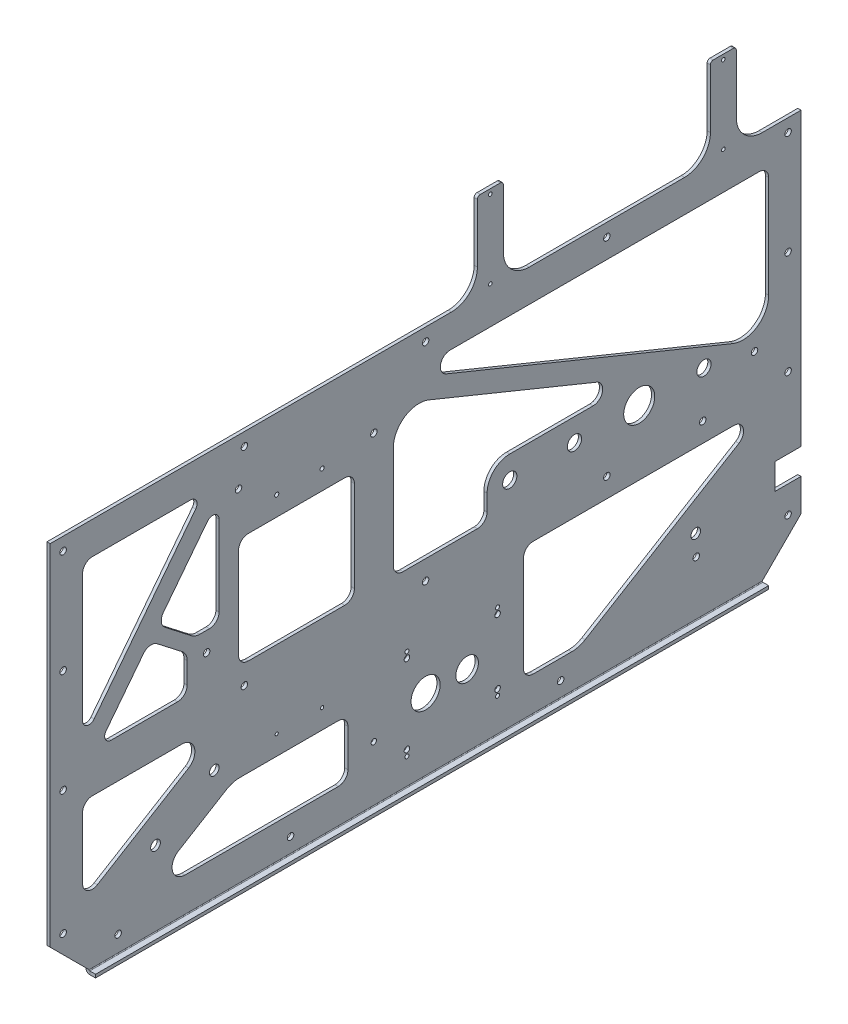
SolidWorks part; units mm, degrees
note: The reader was unsure of these and kept them because the rebuilt part matched: flange length of "Edge-Flange1".
material "6061-T6 (SS)"
ref_plane "Front Plane" through (0, 0, 0) normal (0, 0, 1) x (1, 0, 0)
ref_plane "Top Plane" through (0, 0, 0) normal (0, 1, 0) x (1, 0, 0)
ref_plane "Right Plane" through (0, 0, 0) normal (1, 0, 0) x (0, 0, -1)
sketch "Sketch1" plane through (0, 0, 0) normal (1, 0, 0) x (0, 0, -1)
  line L0 (330.2, 0) -> (-330.2, 0)
  line L1 (-330.2, 0) -> (-368.3, 38.1)
  line L2 (-368.3, 38.1) -> (-368.3, 381)
  line L3 (-368.3, 381) -> (368.3, 381)
  line L4 (368.3, 381) -> (368.3, 38.1)
  line L5 (368.3, 38.1) -> (330.2, 0)
  point P4 (0, 0)
  dimension "D1" = 736.6
  dimension "D2" = 381
  dimension "D3" = 38.1
  dimension "D4" = 45
base flange "Base-Flange1" sketch "Sketch1" thickness 3.175 reverse thickness direction no parameters "D1"=0.7366
sketch "Sketch10" plane through (0, 0, 0) normal (1, 0, 0) x (0, 0, -1)
  line L0 (302.006, 466.725) -> (282.194, 466.725) construction
  line L1 (304.8, 381) -> (279.4, 381)
  line L2 (304.8, 381) -> (304.8, 466.725)
  line L3 (304.8, 466.725) -> (279.4, 466.725)
  line L4 (279.4, 381) -> (279.4, 466.725)
  line L5 (279.4, 463.931) -> (279.4, 406.4) construction
  line L7 (368.3, 381) -> (-368.3, 381) construction
  line L8 (304.8, 406.4) -> (304.8, 463.931) construction
  line L9 (76.2, 381) -> (50.8, 381)
  line L10 (76.2, 381) -> (76.2, 466.725)
  line L11 (76.2, 466.725) -> (50.8, 466.725)
  line L12 (50.8, 381) -> (50.8, 466.725)
  line L13 (76.2, 406.4) -> (76.2, 463.931) construction
  line L15 (50.8, 463.931) -> (50.8, 406.4) construction
base flange "Tab1" sketch "Sketch10" thickness 3.175 reverse thickness direction no parameters "D1"=0.7366
sketch "Sketch6" plane through (0, 0, 0) normal (1, 0, 0) x (0, 0, -1)
  circle A0 centre (264.9792, 73.025) radius 4.7625
  circle A1 centre (0, 69.85) radius 14.2875
  circle A2 centre (-264.9792, 73.025) radius 4.7625
  circle A3 centre (132.4896, 14.2875) radius 3.175 construction
  circle A4 centre (-132.4896, 14.2875) radius 3.175 construction
  circle A5 centre (132.4896, 14.2875) radius 3.175
  circle A6 centre (-264.9792, 73.025) radius 4.7625 construction
  circle A7 centre (0, 69.85) radius 14.2875 construction
  circle A8 centre (264.9792, 73.025) radius 4.7625 construction
  circle A9 centre (-132.4896, 14.2875) radius 3.175
  dimension "D1" = 28.575
  dimension "D2" = 9.525
  dimension "D3" = 9.525
extrude "Cut-Extrude1" cut sketch "Sketch6" against normal through all normal cut yes
sketch "Sketch7" plane through (0, 0, 0) normal (1, 0, 0) x (0, 0, -1)
  line L0 (368.3, 95.25) -> (368.3, 69.85)
  line L1 (209.55, 209.55) -> (146.05, 209.55) construction
  line L2 (368.3, 95.25) -> (342.9, 95.25)
  line L3 (146.05, 209.55) -> (82.55, 209.55) construction
  line L4 (368.3, 69.85) -> (342.9, 69.85)
  line L7 (342.9, 95.25) -> (342.9, 69.85)
  line L8 (349.2669, 95.25) -> (346.0496, 95.25) construction
  line L10 (342.9, 92.1004) -> (342.9, 88.8831) construction
  circle A0 centre (355.6, 43.3605) radius 3.175 construction
  circle A1 centre (355.6, 165.1) radius 3.175 construction
  circle A2 centre (177.8, 165.1) radius 3.175 construction
  circle A3 centre (0, 165.1) radius 3.175 construction
  circle A4 centre (-177.8, 165.1) radius 3.175 construction
  circle A5 centre (-355.6, 43.3605) radius 3.175 construction
  circle A6 centre (-355.6, 165.1) radius 3.175 construction
  circle A7 centre (355.6, 43.3605) radius 3.175
  circle A8 centre (355.6, 165.1) radius 3.175
  circle A9 centre (177.8, 165.1) radius 3.175
  circle A10 centre (0, 165.1) radius 3.175
  circle A11 centre (-177.8, 165.1) radius 3.175
  circle A12 centre (-355.6, 43.3605) radius 3.175
  circle A13 centre (-355.6, 165.1) radius 3.175
  circle A14 centre (-301.625, 15.875) radius 3.175 construction
  circle A15 centre (-214.8334, 211.6192) radius 3.175 construction
  circle A16 centre (-301.625, 15.875) radius 3.175
  circle A17 centre (-214.8334, 211.6192) radius 3.175
  circle A18 centre (-101.6, 311.4675) radius 2.032 construction
  circle A19 centre (-146.05, 311.4675) radius 2.032 construction
  circle A20 centre (-101.6, 311.4675) radius 2.032
  circle A21 centre (-146.05, 311.4675) radius 2.032
  circle A22 centre (82.55, 209.55) radius 6.985
  circle A23 centre (63.5, 461.9625) radius 1.7859 construction
  circle A24 centre (265.525, 52.775) radius 3.175 construction
  circle A25 centre (63.5, 385.7625) radius 1.7859 construction
  circle A26 centre (-146.05, 108.2675) radius 1.5875 construction
  circle A27 centre (-101.6, 108.2675) radius 1.5875 construction
  circle A28 centre (-146.05, 108.2675) radius 1.5875
  circle A29 centre (-101.6, 108.2675) radius 1.5875
  circle A30 centre (273.05, 209.55) radius 6.985
  circle A31 centre (209.55, 209.55) radius 15.24
  circle A32 centre (146.05, 209.55) radius 6.985
  circle A33 centre (271.875, 165.1) radius 3.175 construction
  circle A34 centre (273.05, 209.55) radius 6.9024 construction
  circle A35 centre (146.05, 209.55) radius 6.9024 construction
  circle A36 centre (209.55, 209.55) radius 13.97 construction
  circle A37 centre (292.1, 461.9625) radius 1.7859 construction
  circle A38 centre (355.6, 266.7) radius 3.175 construction
  circle A39 centre (322.675, 198.825) radius 3.175 construction
  circle A40 centre (265.525, 52.775) radius 3.175
  circle A41 centre (271.875, 165.1) radius 3.175
  circle A42 centre (292.1, 385.7625) radius 1.7859 construction
  circle A43 centre (63.5, 461.9625) radius 1.7859
  circle A44 centre (-50.8, 316.23) radius 3.175 construction
  circle A45 centre (-50.8, 316.23) radius 3.175
  circle A46 centre (355.6, 368.3) radius 3.175 construction
  circle A47 centre (177.8, 368.3) radius 3.175 construction
  circle A48 centre (0, 368.3) radius 3.175 construction
  circle A49 centre (-177.8, 368.3) radius 3.175 construction
  circle A50 centre (-355.6, 368.3) radius 3.175 construction
  circle A51 centre (-355.6, 266.7) radius 3.175 construction
  circle A52 centre (355.6, 266.7) radius 3.175
  circle A53 centre (355.6, 368.3) radius 3.175
  circle A54 centre (177.8, 368.3) radius 3.175
  circle A55 centre (0, 368.3) radius 3.175
  circle A56 centre (-177.8, 368.3) radius 3.175
  circle A57 centre (-355.6, 368.3) radius 3.175
  circle A58 centre (-355.6, 266.7) radius 3.175
  circle A59 centre (322.675, 198.825) radius 3.175
  circle A62 centre (292.1, 461.9625) radius 1.7859
  circle A63 centre (63.5, 385.7625) radius 1.7859
  circle A64 centre (292.1, 385.7625) radius 1.7859
  dimension "D4" = 13.97
  dimension "D5" = 30.48
  dimension "D1" = 25.4
extrude "Cut-Extrude2" cut sketch "Sketch7" against normal through all normal cut yes
sketch "Sketch8" plane through (0, 0, 0) normal (1, 0, 0) x (0, 0, -1)
  circle A0 centre (70.5879, 107.442) radius 1.9514 construction
  circle A1 centre (70.5879, 101.6) radius 2.7261 construction
  circle A2 centre (-18.3121, 114.427) radius 1.9514 construction
  circle A3 centre (-18.3121, 108.585) radius 2.7261 construction
  circle A4 centre (-18.3121, 31.115) radius 2.7261 construction
  circle A5 centre (-18.3121, 25.273) radius 1.9514 construction
  circle A6 centre (70.5879, 38.1) radius 2.7261 construction
  circle A7 centre (70.5879, 32.258) radius 1.9514 construction
  circle A8 centre (70.5879, 107.442) radius 1.9514
  circle A9 centre (70.5879, 101.6) radius 2.7261
  circle A10 centre (-18.3121, 114.427) radius 1.9514
  circle A11 centre (-18.3121, 108.585) radius 2.7261
  circle A12 centre (-18.3121, 31.115) radius 2.7261
  circle A13 centre (-18.3121, 25.273) radius 1.9514
  circle A14 centre (70.5879, 38.1) radius 2.7261
  circle A15 centre (70.5879, 32.258) radius 1.9514
  circle A16 centre (40.7162, 69.85) radius 11.1125 construction
  circle A17 centre (40.7162, 69.85) radius 11.1125
extrude "Cut-Extrude3" cut sketch "Sketch8" against normal through all normal cut yes
sketch "Sketch9" plane through (0, 0, 0) normal (1, 0, 0) x (0, 0, -1)
  circle A0 centre (-207.3469, 108.0375) radius 4.7625 construction
  circle A1 centre (-183.5344, 335.05) radius 3.175 construction
  circle A2 centre (-183.5344, 335.05) radius 3.175
  circle A3 centre (-207.3469, 108.0375) radius 4.7625
  circle A4 centre (-50.8, 53.975) radius 2.6035 construction
  circle A5 centre (-50.8, 53.975) radius 2.6035
extrude "Cut-Extrude4" cut sketch "Sketch9" against normal through all normal cut yes
fillet "Fillet1" [suppressed] radius 1.5875
fillet "Fillet2" radius 2.794 4 edges at (-1.5875, 466.725, -279.4) (-1.5875, 466.725, -304.8) (-1.5875, 466.725, -76.2) (-1.5875, 466.725, -50.8)
fillet "Fillet3" radius 25.4 4 edges at (-1.5875, 381, -279.4) (-1.5875, 381, -304.8) (-1.5875, 381, -76.2) (-1.5875, 381, -50.8)
sketch "Sketch11" plane through (0, 0, 0) normal (1, 0, 0) x (0, 0, -1)
  line L0 (-355.6, 165.1) -> (-355.6, 368.3) construction
  line L1 (-355.6, 368.3) -> (355.6, 368.3) construction
  line L2 (355.6, 368.3) -> (355.6, 165.1) construction
  line L3 (327.025, 349.25) -> (23.9702, 349.25) construction
  line L4 (20.3691, 330.907) -> (301.5471, 216.0804) construction
  line L5 (336.55, 239.5952) -> (336.55, 339.725) construction
  line L6 (327.025, 349.25) -> (23.9702, 349.25)
  line L7 (20.3691, 330.907) -> (301.5471, 216.0804)
  line L8 (336.55, 239.5952) -> (336.55, 339.725)
  line L10 (302.4269, 146.05) -> (105.5129, 146.05) construction
  line L12 (-355.6, 165.1) -> (355.6, 165.1) construction
  line L13 (95.9879, 136.525) -> (95.9879, 42.8625) construction
  line L14 (156.451, 37.0096) -> (307.36, 128.377) construction
  line L15 (105.5129, 33.3375) -> (143.2959, 33.3375) construction
  line L16 (302.4269, 146.05) -> (105.5129, 146.05)
  line L17 (95.9879, 136.525) -> (95.9879, 42.8625)
  line L18 (156.451, 37.0096) -> (307.36, 128.377)
  line L19 (105.5129, 33.3375) -> (143.2959, 33.3375)
  line L20 (-236.0213, 33.3375) -> (-85.725, 33.3375) construction
  line L21 (-76.2, 42.8625) -> (-76.2, 79.6925) construction
  line L22 (-85.725, 89.2175) -> (-182.2944, 89.2175) construction
  line L23 (-195.4823, 85.5255) -> (-242.6153, 56.8915) construction
  line L24 (-236.0213, 33.3375) -> (-85.725, 33.3375)
  line L25 (-76.2, 42.8625) -> (-76.2, 79.6925)
  line L26 (-85.725, 89.2175) -> (-182.2944, 89.2175)
  line L27 (-195.4823, 85.5255) -> (-242.6153, 56.8915)
  line L28 (-322.0795, 68.0556) -> (-232.4679, 122.496) construction
  line L29 (-239.0619, 146.05) -> (-327.025, 146.05) construction
  line L30 (-336.55, 136.525) -> (-336.55, 76.1961) construction
  line L31 (-322.0795, 68.0556) -> (-232.4679, 122.496)
  line L32 (-239.0619, 146.05) -> (-327.025, 146.05)
  line L33 (-336.55, 136.525) -> (-336.55, 76.1961)
  line L34 (-325.1809, 210.4894) -> (-225.5776, 339.0102) construction
  line L35 (-336.55, 339.725) -> (-336.55, 214.3792) construction
  line L36 (-230.5968, 349.25) -> (-327.025, 349.25) construction
  line L37 (-325.1809, 210.4894) -> (-225.5776, 339.0102)
  line L38 (-336.55, 339.725) -> (-336.55, 214.3792)
  line L39 (-230.5968, 349.25) -> (-327.025, 349.25)
  line L40 (-255.646, 253.5644) -> (-229.5382, 233.3309) construction
  line L41 (-221.7586, 230.6692) -> (-212.1094, 230.6692) construction
  line L42 (-202.5844, 240.1942) -> (-202.5844, 319.0208) construction
  line L43 (-213.9535, 322.9106) -> (-257.34, 266.9278) construction
  line L44 (-255.646, 253.5644) -> (-229.5382, 233.3309)
  line L45 (-221.7586, 230.6692) -> (-212.1094, 230.6692)
  line L46 (-202.5844, 240.1942) -> (-202.5844, 319.0208)
  line L47 (-213.9535, 322.9106) -> (-257.34, 266.9278)
  line L48 (-308.5376, 184.15) -> (-243.4084, 184.15) construction
  line L49 (-233.8834, 193.675) -> (-233.8834, 214.4059) construction
  line L50 (-238.8038, 224.4442) -> (-263.4257, 243.5261) construction
  line L51 (-276.7891, 241.8321) -> (-313.5567, 194.3898) construction
  line L52 (-308.5376, 184.15) -> (-243.4084, 184.15)
  line L53 (-233.8834, 193.675) -> (-233.8834, 214.4059)
  line L54 (-238.8038, 224.4442) -> (-263.4257, 243.5261)
  line L55 (-276.7891, 241.8321) -> (-313.5567, 194.3898)
  line L56 (-183.5344, 282.8925) -> (-183.5344, 193.675) construction
  line L57 (-174.0094, 184.15) -> (-79.375, 184.15) construction
  line L58 (-69.85, 193.675) -> (-69.85, 282.8925) construction
  line L59 (-79.375, 292.4175) -> (-174.0094, 292.4175) construction
  line L60 (-183.5344, 282.8925) -> (-183.5344, 193.675)
  line L61 (-174.0094, 184.15) -> (-79.375, 184.15)
  line L62 (-69.85, 193.675) -> (-69.85, 282.8925)
  line L63 (-79.375, 292.4175) -> (-174.0094, 292.4175)
  line L64 (-31.75, 293.8048) -> (-31.75, 193.675) construction
  line L65 (284.4309, 202.493) -> (3.2529, 317.3196) construction
  line L66 (-31.75, 293.8048) -> (-31.75, 193.675)
  line L67 (167.8106, 250.118) -> (3.2529, 317.3196)
  line L68 (164.2095, 231.775) -> (82.55, 231.775)
  line L69 (60.325, 209.55) -> (60.325, 193.675)
  line L70 (50.8, 184.15) -> (-22.225, 184.15)
  arc A0 (336.55, 339.725) -> (327.025, 349.25) centre (327.025, 339.725) ccw construction
  arc A1 (23.9702, 349.25) -> (20.3691, 330.907) centre (23.9702, 339.725) ccw construction
  arc A2 (301.5471, 216.0804) -> (336.55, 239.5952) centre (311.15, 239.5952) ccw construction
  arc A3 (336.55, 339.725) -> (327.025, 349.25) centre (327.025, 339.725) ccw
  arc A4 (23.9702, 349.25) -> (20.3691, 330.907) centre (23.9702, 339.725) ccw
  arc A5 (301.5471, 216.0804) -> (336.55, 239.5952) centre (311.15, 239.5952) ccw
  arc A6 (307.36, 128.377) -> (302.4269, 146.05) centre (302.4269, 136.525) ccw construction
  arc A7 (105.5129, 146.05) -> (95.9879, 136.525) centre (105.5129, 136.525) ccw construction
  arc A8 (143.2959, 33.3375) -> (156.451, 37.0096) centre (143.2959, 58.7375) ccw construction
  arc A9 (95.9879, 42.8625) -> (105.5129, 33.3375) centre (105.5129, 42.8625) ccw construction
  arc A10 (307.36, 128.377) -> (302.4269, 146.05) centre (302.4269, 136.525) ccw
  arc A12 (105.5129, 146.05) -> (95.9879, 136.525) centre (105.5129, 136.525) ccw
  arc A13 (143.2959, 33.3375) -> (156.451, 37.0096) centre (143.2959, 58.7375) ccw
  arc A16 (95.9879, 42.8625) -> (105.5129, 33.3375) centre (105.5129, 42.8625) ccw
  arc A17 (-242.6153, 56.8915) -> (-236.0213, 33.3375) centre (-236.0213, 46.0375) ccw construction
  arc A18 (-85.725, 33.3375) -> (-76.2, 42.8625) centre (-85.725, 42.8625) ccw construction
  arc A19 (-76.2, 79.6925) -> (-85.725, 89.2175) centre (-85.725, 79.6925) ccw construction
  arc A22 (-182.2944, 89.2175) -> (-195.4823, 85.5255) centre (-182.2944, 63.8175) ccw construction
  arc A23 (-242.6153, 56.8915) -> (-236.0213, 33.3375) centre (-236.0213, 46.0375) ccw
  arc A25 (-85.725, 33.3375) -> (-76.2, 42.8625) centre (-85.725, 42.8625) ccw
  arc A26 (-76.2, 79.6925) -> (-85.725, 89.2175) centre (-85.725, 79.6925) ccw
  arc A27 (-182.2944, 89.2175) -> (-195.4823, 85.5255) centre (-182.2944, 63.8175) ccw
  arc A28 (-336.55, 76.1961) -> (-322.0795, 68.0556) centre (-327.025, 76.1961) ccw construction
  arc A32 (-232.4679, 122.496) -> (-239.0619, 146.05) centre (-239.0619, 133.35) ccw construction
  arc A33 (-327.025, 146.05) -> (-336.55, 136.525) centre (-327.025, 136.525) ccw construction
  arc A34 (-336.55, 76.1961) -> (-322.0795, 68.0556) centre (-327.025, 76.1961) ccw
  arc A35 (-232.4679, 122.496) -> (-239.0619, 146.05) centre (-239.0619, 133.35) ccw
  arc A36 (-327.025, 146.05) -> (-336.55, 136.525) centre (-327.025, 136.525) ccw
  arc A37 (-336.55, 214.3792) -> (-325.1809, 210.4894) centre (-330.2, 214.3792) ccw construction
  arc A38 (-225.5776, 339.0102) -> (-230.5968, 349.25) centre (-230.5968, 342.9) ccw construction
  arc A39 (-327.025, 349.25) -> (-336.55, 339.725) centre (-327.025, 339.725) ccw construction
  arc A40 (-336.55, 214.3792) -> (-325.1809, 210.4894) centre (-330.2, 214.3792) ccw
  arc A41 (-225.5776, 339.0102) -> (-230.5968, 349.25) centre (-230.5968, 342.9) ccw
  arc A42 (-327.025, 349.25) -> (-336.55, 339.725) centre (-327.025, 339.725) ccw
  arc A43 (-257.34, 266.9278) -> (-255.646, 253.5644) centre (-249.8113, 261.0931) ccw construction
  arc A44 (-229.5382, 233.3309) -> (-221.7586, 230.6692) centre (-221.7586, 243.3692) ccw construction
  arc A45 (-212.1094, 230.6692) -> (-202.5844, 240.1942) centre (-212.1094, 240.1942) ccw construction
  arc A46 (-202.5844, 319.0208) -> (-213.9535, 322.9106) centre (-208.9344, 319.0208) ccw construction
  arc A47 (-257.34, 266.9278) -> (-255.646, 253.5644) centre (-249.8113, 261.0931) ccw
  arc A48 (-229.5382, 233.3309) -> (-221.7586, 230.6692) centre (-221.7586, 243.3692) ccw
  arc A49 (-212.1094, 230.6692) -> (-202.5844, 240.1942) centre (-212.1094, 240.1942) ccw
  arc A50 (-202.5844, 319.0208) -> (-213.9535, 322.9106) centre (-208.9344, 319.0208) ccw
  arc A51 (-243.4084, 184.15) -> (-233.8834, 193.675) centre (-243.4084, 193.675) ccw construction
  arc A52 (-233.8834, 214.4059) -> (-238.8038, 224.4442) centre (-246.5834, 214.4059) ccw construction
  arc A53 (-263.4257, 243.5261) -> (-276.7891, 241.8321) centre (-269.2604, 235.9974) ccw construction
  arc A54 (-313.5567, 194.3898) -> (-308.5376, 184.15) centre (-308.5376, 190.5) ccw construction
  arc A55 (-243.4084, 184.15) -> (-233.8834, 193.675) centre (-243.4084, 193.675) ccw
  arc A56 (-233.8834, 214.4059) -> (-238.8038, 224.4442) centre (-246.5834, 214.4059) ccw
  arc A57 (-263.4257, 243.5261) -> (-276.7891, 241.8321) centre (-269.2604, 235.9974) ccw
  arc A58 (-313.5567, 194.3898) -> (-308.5376, 184.15) centre (-308.5376, 190.5) ccw
  arc A59 (-174.0094, 292.4175) -> (-183.5344, 282.8925) centre (-174.0094, 282.8925) ccw construction
  arc A60 (-79.375, 184.15) -> (-69.85, 193.675) centre (-79.375, 193.675) ccw construction
  arc A61 (-183.5344, 193.675) -> (-174.0094, 184.15) centre (-174.0094, 193.675) ccw construction
  arc A62 (-69.85, 282.8925) -> (-79.375, 292.4175) centre (-79.375, 282.8925) ccw construction
  arc A63 (-174.0094, 292.4175) -> (-183.5344, 282.8925) centre (-174.0094, 282.8925) ccw
  arc A64 (-79.375, 184.15) -> (-69.85, 193.675) centre (-79.375, 193.675) ccw
  arc A65 (-183.5344, 193.675) -> (-174.0094, 184.15) centre (-174.0094, 193.675) ccw
  arc A66 (-69.85, 282.8925) -> (-79.375, 292.4175) centre (-79.375, 282.8925) ccw
  arc A67 (-31.75, 193.675) -> (-22.225, 184.15) centre (-22.225, 193.675) ccw construction
  arc A68 (3.2529, 317.3196) -> (-31.75, 293.8048) centre (-6.35, 293.8048) ccw construction
  arc A69 (-31.75, 193.675) -> (-22.225, 184.15) centre (-22.225, 193.675) ccw
  arc A70 (3.2529, 317.3196) -> (-31.75, 293.8048) centre (-6.35, 293.8048) ccw
  arc A71 (164.2095, 231.775) -> (167.8106, 250.118) centre (164.2095, 241.3) ccw
  arc A72 (82.55, 231.775) -> (60.325, 209.55) centre (82.55, 209.55) ccw
  arc A73 (60.325, 193.675) -> (50.8, 184.15) centre (50.8, 193.675) cw
  circle A74 centre (82.55, 209.55) radius 6.985 construction
  point P110 (209.55, 209.55)
  dimension "D1" = 22.225
extrude "Cut-Extrude5" cut sketch "Sketch11" against normal through all normal cut yes
sketch "Sketch12" plane through (-3.175, 0, 0) normal (-1, 0, 0) x (0, 0, 1)
  circle A0 centre (50.8, 316.23) radius 7.1633
  circle A1 centre (101.6, 311.4675) radius 5.9946
  circle A2 centre (146.05, 311.4675) radius 5.636
  circle A3 centre (101.6, 108.2675) radius 5.1307
  circle A4 centre (146.05, 108.2675) radius 4.8995
  circle A5 centre (50.8, 53.975) radius 6.7961
split line "Split Line1" [suppressed]
sketch "Sketch13" [suppressed] plane through (-3.175, 0, 0) normal (-1, 0, 0) x (0, 0, 1)
  line L0 (175.0557, 65.082) -> (99.2778, 65.082) construction
  line L1 (175.0557, 39.5069) -> (99.2778, 39.5069)
  line L2 (175.0557, 90.657) -> (99.2778, 90.657)
  line L3 (-286.6408, 115.1513) -> (-122.4649, 115.1513) construction
  line L4 (-286.6408, 140.992) -> (-122.4649, 140.992)
  line L5 (-286.6408, 89.3106) -> (-122.4649, 89.3106)
  line L6 (-286.6408, 39.5069) -> (-158.377, 39.5069) construction
  line L7 (-286.6408, 56.1499) -> (-158.377, 56.1499)
  line L8 (-286.6408, 22.864) -> (-158.377, 22.864)
  line L9 (257.8929, 123.8055) -> (337.2942, 123.8055) construction
  line L10 (257.8929, 142.1289) -> (337.2942, 142.1289)
  line L11 (257.8929, 105.4821) -> (337.2942, 105.4821)
  line L12 (175.0557, 130.3079) -> (49.1477, 130.3079) construction
  line L13 (175.0557, 121.6039) -> (49.1477, 121.6039)
  line L14 (175.0557, 139.012) -> (49.1477, 139.012)
  arc A0 (175.0557, 39.5069) -> (175.0557, 90.657) centre (175.0557, 65.082) ccw
  arc A1 (99.2778, 90.657) -> (99.2778, 39.5069) centre (99.2778, 65.082) ccw
  arc A2 (-286.6408, 140.992) -> (-286.6408, 89.3106) centre (-286.6408, 115.1513) ccw
  arc A3 (-122.4649, 89.3106) -> (-122.4649, 140.992) centre (-122.4649, 115.1513) ccw
  arc A4 (-286.6408, 56.1499) -> (-286.6408, 22.864) centre (-286.6408, 39.5069) ccw
  arc A5 (-158.377, 22.864) -> (-158.377, 56.1499) centre (-158.377, 39.5069) ccw
  arc A6 (257.8929, 142.1289) -> (257.8929, 105.4821) centre (257.8929, 123.8055) ccw
  arc A7 (337.2942, 105.4821) -> (337.2942, 142.1289) centre (337.2942, 123.8055) ccw
  arc A8 (175.0557, 121.6039) -> (175.0557, 139.012) centre (175.0557, 130.3079) ccw
  arc A9 (49.1477, 139.012) -> (49.1477, 121.6039) centre (49.1477, 130.3079) ccw
  point P2 (137.1667, 65.082)
  point P7 (-204.5528, 115.1513)
  point P14 (-222.5089, 39.5069)
  point P21 (297.5935, 123.8055)
  point P30 (112.1017, 130.3079)
extrude "Cut-Extrude6" [suppressed] cut sketch "Sketch13" against normal through all
edge flange "Edge-Flange1" sketch "Sketch16" flange angle 90 flange length 9.525 flange position bend outside bend radius 0.7366 thickness 3.175 relief rectangular parameters "D6"=10
sketch "Sketch16" plane through (0, 0, 0) normal (0, -1, 0) x (0, 0, -1)
  line L2 (-330.2, 0) -> (-330.2, 6.35)
  line L3 (-330.2, 6.35) -> (330.2, 6.35)
  line L4 (330.2, 6.35) -> (330.2, 0)
  line L5 (-330.2, 0) -> (330.2, 0) construction
  line L6 (-330.2, 0) -> (330.2, 0)
bend "EdgeBend1" bend radius 0.7366 bend angle 90 parameters "D5"=1
sketch "Bend-Lines1" [suppressed] plane through (0, 0, 0) normal (0, 1, 0) x (1, 0, 0)
sketch "Bounding-Box1" [suppressed] plane through (0, 0, 0) normal (0, 1, 0) x (1, 0, 0)
sheet metal parameters "Sheet-Metal1" thickness 3.175 parameters "D1"=0.7366
flat pattern "Flat-Pattern1" [suppressed]
sketch "Bend-Lines2" plane through (0, 0, 0) normal (0, 1, 0) x (1, 0, 0)
sketch3d "Bounding-Box2" [suppressed]
  line L0 (368.3, 0, 0) -> (-368.3, 0, 0) construction
  line L1 (368.3, 381, 0) -> (-368.3, 381, 0) construction
  line L2 (368.3, 0, 0) -> (368.3, 381, 0) construction
  line L3 (-368.3, 0, 0) -> (-368.3, 381, 0) construction
sheet metal parameters "Sheet-Metal2" thickness 3.175 parameters "D1"=0.7366
flat pattern "Flat-Pattern6"
sketch "Bend-Lines3" plane through (0, 0, 0) normal (0, 1, 0) x (1, 0, 0)
sketch3d "Bounding-Box3" [suppressed]
  line L0 (368.3, 0, 0) -> (-368.3, 0, 0) construction
  line L1 (368.3, 466.725, 0) -> (-368.3, 466.725, 0) construction
  line L2 (368.3, 0, 0) -> (368.3, 466.725, 0) construction
  line L3 (-368.3, 0, 0) -> (-368.3, 466.725, 0) construction
sheet metal parameters "Sheet-Metal3" thickness 3.175 parameters "D1"=0.7366
flat pattern "Flat-Pattern6"
sketch "Bend-Lines3" plane through (0, 0, 0) normal (0, 1, 0) x (1, 0, 0)
sketch3d "Bounding-Box3" [suppressed]
  line L0 (368.3, 0, 0) -> (-368.3, 0, 0) construction
  line L1 (368.3, 466.725, 0) -> (-368.3, 466.725, 0) construction
  line L2 (368.3, 0, 0) -> (368.3, 466.725, 0) construction
  line L3 (-368.3, 0, 0) -> (-368.3, 466.725, 0) construction
sheet metal parameters "Sheet-Metal4" thickness 3.175 parameters "D1"=0.7366
flat pattern "Flat-Pattern6"
sketch "Bend-Lines3" plane through (0, 0, 0) normal (0, 1, 0) x (1, 0, 0)
sketch3d "Bounding-Box3" [suppressed]
  line L0 (368.3, 0, 0) -> (-368.3, 0, 0) construction
  line L1 (368.3, 466.725, 0) -> (-368.3, 466.725, 0) construction
  line L2 (368.3, 0, 0) -> (368.3, 466.725, 0) construction
  line L3 (-368.3, 0, 0) -> (-368.3, 466.725, 0) construction
sheet metal parameters "Sheet-Metal5" thickness 3.175 parameters "D1"=0.7366
flat pattern "Flat-Pattern6"
sketch "Bend-Lines3" plane through (0, 0, 0) normal (0, 1, 0) x (1, 0, 0)
sketch3d "Bounding-Box3" [suppressed]
  line L0 (368.3, 0, 0) -> (-368.3, 0, 0) construction
  line L1 (368.3, 466.725, 0) -> (-368.3, 466.725, 0) construction
  line L2 (368.3, 0, 0) -> (368.3, 466.725, 0) construction
  line L3 (-368.3, 0, 0) -> (-368.3, 466.725, 0) construction
sheet metal parameters "Sheet-Metal6" thickness 3.175 parameters "D1"=0.7366
flat pattern "Flat-Pattern6"
sketch "Bend-Lines3" plane through (0, 0, 0) normal (0, 1, 0) x (1, 0, 0)
sketch3d "Bounding-Box3" [suppressed]
  line L0 (368.3, 0, 0) -> (-368.3, 0, 0) construction
  line L1 (368.3, 466.725, 0) -> (-368.3, 466.725, 0) construction
  line L2 (368.3, 0, 0) -> (368.3, 466.725, 0) construction
  line L3 (-368.3, 0, 0) -> (-368.3, 466.725, 0) construction
sheet metal parameters "Sheet-Metal7" thickness 3.175 parameters "D1"=0.7366
flat pattern "Flat-Pattern6"
sketch "Bend-Lines3" plane through (0, 0, 0) normal (0, 1, 0) x (1, 0, 0)
sketch3d "Bounding-Box3" [suppressed]
  line L0 (368.3, 0, 0) -> (-368.3, 0, 0) construction
  line L1 (368.3, 466.725, 0) -> (-368.3, 466.725, 0) construction
  line L2 (368.3, 0, 0) -> (368.3, 466.725, 0) construction
  line L3 (-368.3, 0, 0) -> (-368.3, 466.725, 0) construction
sheet metal parameters "Sheet-Metal11" thickness 3.175 parameters "D1"=0.7366
flat pattern "Flat-Pattern6"
sketch "Bend-Lines3" plane through (0, 0, 0) normal (0, 1, 0) x (1, 0, 0)
sketch3d "Bounding-Box3" [suppressed]
  line L0 (368.3, 0, 0) -> (-368.3, 0, 0) construction
  line L1 (368.3, 466.725, 0) -> (-368.3, 466.725, 0) construction
  line L2 (368.3, 0, 0) -> (368.3, 466.725, 0) construction
  line L3 (-368.3, 0, 0) -> (-368.3, 466.725, 0) construction
sheet metal parameters "Sheet-Metal14" thickness 3.175 parameters "D1"=0.7366
flat pattern "Flat-Pattern6"
sketch "Bend-Lines3" plane through (0, 0, 0) normal (0, 1, 0) x (1, 0, 0)
sketch3d "Bounding-Box3" [suppressed]
  line L0 (368.3, 0, 0) -> (-368.3, 0, 0) construction
  line L1 (368.3, 466.725, 0) -> (-368.3, 466.725, 0) construction
  line L2 (368.3, 0, 0) -> (368.3, 466.725, 0) construction
  line L3 (-368.3, 0, 0) -> (-368.3, 466.725, 0) construction
sheet metal parameters "Sheet-Metal18" thickness 3.175 parameters "D1"=0.7366
flat pattern "Flat-Pattern6"
sketch "Bend-Lines3" plane through (0, 0, 0) normal (1, 0, 0) x (0, 0, -1)
  line L0 (-330.2, -1.8253) -> (330.2, -1.8253) construction
  line L1 (-330.2, -1.8253) -> (330.2, -1.8253) construction
sketch3d "Bounding-Box3" [suppressed]
  line L0 (368.3, -9.2641, 0) -> (-368.3, -9.2641, 0) construction
  line L1 (368.3, 466.725, 0) -> (-368.3, 466.725, 0) construction
  line L2 (368.3, -9.2641, 0) -> (368.3, 466.725, 0) construction
  line L3 (-368.3, -9.2641, 0) -> (-368.3, 466.725, 0) construction
bend of the flat pattern "Flatten-<EdgeBend1>1"
